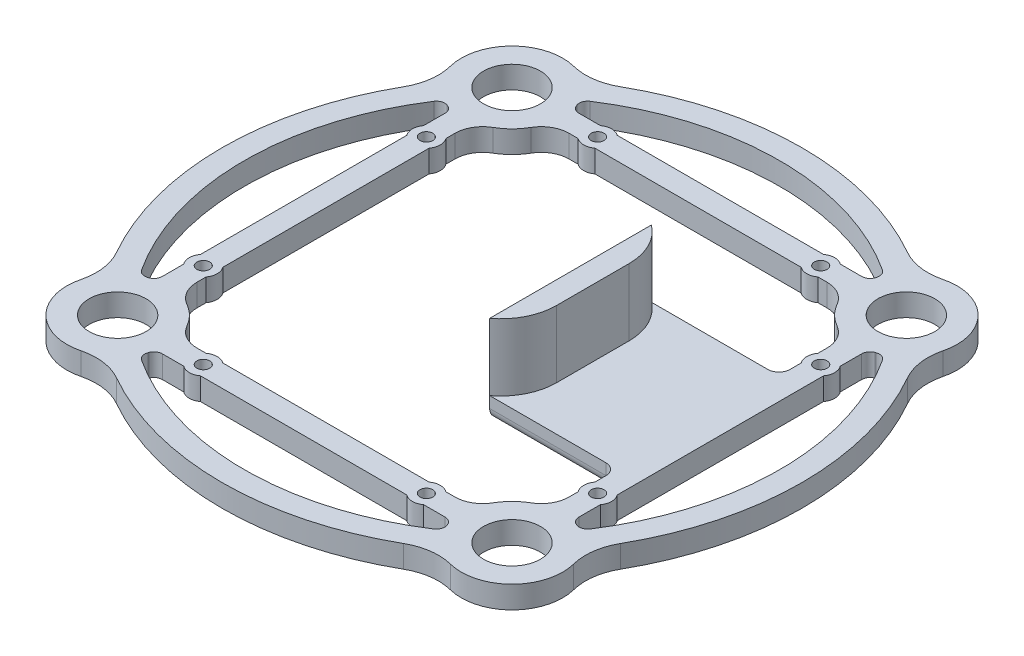
SolidWorks part; units mm, degrees
ref_plane "Front Plane" through (0, 0, 0) normal (0, 0, 1) x (1, 0, 0)
ref_plane "Top Plane" through (0, 0, 0) normal (0, 1, 0) x (1, 0, 0)
ref_plane "Right Plane" through (0, 0, 0) normal (1, 0, 0) x (0, 0, -1)
sketch "Sketch1" plane through (0, 0, 0) normal (0, 1, 0) x (1, 0, 0)
  line L1 (-35.3553, -35.3553) -> (35.3553, -35.3553) construction
  line L2 (-35.3553, -35.3553) -> (-35.3553, 35.3553) construction
  line L3 (-35.3553, 35.3553) -> (35.3553, 35.3553) construction
  line L4 (35.3553, -35.3553) -> (35.3553, 35.3553) construction
  line L5 (-35.3553, -35.3553) -> (35.3553, 35.3553) construction
  line L6 (-35.3553, 35.3553) -> (35.3553, -35.3553) construction
  circle A0 centre (0, 0) radius 52
  circle A1 centre (0, 0) radius 50 construction
  circle A2 centre (0, 0) radius 48
  circle A3 centre (35.3553, 35.3553) radius 5.1
  circle A4 centre (35.3553, 35.3553) radius 9.1
  circle A5 centre (-35.3553, 35.3553) radius 9.1
  circle A6 centre (-35.3553, 35.3553) radius 5.1
  circle A7 centre (-35.3553, -35.3553) radius 9.1
  circle A8 centre (-35.3553, -35.3553) radius 5.1
  circle A9 centre (35.3553, -35.3553) radius 5.1
  circle A10 centre (35.3553, -35.3553) radius 9.1
  dimension "D1" = 96
  dimension "D2" = 100
  dimension "D3" = 104
  dimension "D4" = 10.2
  dimension "D5" = 10.2
  dimension "D6" = 10.2
  dimension "D7" = 10.2
  dimension "D8" = 18.2
  dimension "D9" = 18.2
  dimension "D10" = 18.2
  dimension "D11" = 18.2
extrude "Boss-Extrude1" add sketch "Sketch1" along normal blind 4 contours A7 A2 A5 A0 | A5 A2 A4 A0 | A10 A0 A4 A2 | A10 A2 A7 A0 | A8 A2 A7 | A8 A2 A7 A0 | A8 A0 A7 | A8 A0 A7 A2 | A2 A10 A9 | A0 A10 A2 A9 | A0 A10 A9 | A2 A10 A0 A9 | A0 A4 A2 A3 | A2 A4 A0 A3 | A0 A4 A3 | A2 A4 A3 | A6 A2 A5 A0 | A6 A0 A5 A2 | A6 A0 A5 | A6 A2 A5 region at (49.0102, 0, 15.4585) region at (39.943, 0, -30.075) region at (39.073, 0, -39.073) region at (39.073, 0, 39.073) region at (39.943, 0, 30.075) region at (31.3721, 0, -31.3721) region at (31.3721, 0, 31.3721) region at (30.075, 0, -39.943) region at (0, 0, -48.6096) region at (30.075, 0, 39.943) region at (0, 0, 51.3904) region at (-31.3721, 0, -31.3721) region at (-30.075, 0, -39.943) region at (-39.073, 0, -39.073) region at (-39.073, 0, 39.073) region at (-30.075, 0, 39.943) region at (-31.3721, 0, 31.3721) region at (-41.5843, 0, -27.9071) region at (-39.943, 0, -30.075) region at (-39.943, 0, 30.075)
sketch "Sketch2" plane through (0, 4, 0) normal (0, 1, 0) x (1, 0, 0)
  line L0 (-33.3553, 26.4778) -> (-33.3553, -26.4778)
  line L1 (35.3553, -35.3553) -> (-35.3553, -35.3553) construction
  line L2 (35.3553, -35.3553) -> (35.3553, 35.3553) construction
  line L3 (35.3553, 35.3553) -> (-35.3553, 35.3553) construction
  line L4 (-35.3553, -35.3553) -> (-35.3553, 35.3553) construction
  line L5 (35.3553, -35.3553) -> (-35.3553, 35.3553) construction
  line L6 (35.3553, 35.3553) -> (-35.3553, -35.3553) construction
  line L7 (-37.3553, 26.4778) -> (-37.3553, -26.4778)
  line L8 (-26.4778, 37.3553) -> (26.4778, 37.3553)
  line L9 (-26.4778, 33.3553) -> (26.4778, 33.3553)
  line L10 (37.3553, 26.4778) -> (37.3553, -26.4778)
  line L11 (33.3553, 26.4778) -> (33.3553, -26.4778)
  line L12 (-26.4778, -33.3553) -> (26.4778, -33.3553)
  line L13 (-26.4778, -37.3553) -> (26.4778, -37.3553)
  arc A0 (-39.5091, 27.2586) -> (-27.2586, 39.5091) centre (-35.3553, 35.3553) ccw construction
  arc A1 (-27.2586, -39.5091) -> (-39.5091, -27.2586) centre (-35.3553, -35.3553) ccw construction
  arc A2 (27.2586, 39.5091) -> (39.5091, 27.2586) centre (35.3553, 35.3553) ccw construction
  arc A3 (39.5091, -27.2586) -> (27.2586, -39.5091) centre (35.3553, -35.3553) ccw construction
  circle A4 centre (-35.3553, 35.3553) radius 9.1
  circle A5 centre (35.3553, 35.3553) radius 9.1
  circle A6 centre (35.3553, -35.3553) radius 9.1
  circle A7 centre (-35.3553, -35.3553) radius 9.1
  point P0 (0, 0)
  arc M14 (-27.2586, -39.5091) -> (-39.5091, -27.2586) centre (-35.3553, -35.3553) ccw
  arc M16 (-39.5091, 27.2586) -> (-27.2586, 39.5091) centre (-35.3553, 35.3553) ccw
  arc M18 (27.2586, 39.5091) -> (39.5091, 27.2586) centre (35.3553, 35.3553) ccw
  arc M20 (39.5091, -27.2586) -> (27.2586, -39.5091) centre (35.3553, -35.3553) ccw
  dimension "D1" = 2
  dimension "D2" = 2
  dimension "D3" = 2
  dimension "D4" = 2
  dimension "D5" = 2
  dimension "D6" = 2
  dimension "D7" = 2
  dimension "D8" = 2
extrude "Boss-Extrude2" add sketch "Sketch2" against normal blind 4 contours L9 L8 M16 M18 | L7 L0 M16 M14 | L11 L10 M18 M20 | L13 L12 M14 M20 region at (-35.3553, 4, 0) region at (0, 4, -35.3553) region at (0, 4, 35.3553) region at (35.3553, 4, 0)
sketch "Sketch3" plane through (0, 4, 0) normal (0, 1, 0) x (1, 0, 0)
  line L0 (-26.4778, 33.3553) -> (26.4778, 33.3553) construction
  line L1 (-35.3553, 20) -> (35.3553, 20) construction
  line L2 (-35.3553, 20) -> (-35.3553, -20) construction
  line L3 (-35.3553, -20) -> (35.3553, -20) construction
  line L4 (35.3553, 20) -> (35.3553, -20) construction
  line L5 (-35.3553, 20) -> (35.3553, -20) construction
  line L6 (-35.3553, -20) -> (35.3553, 20) construction
  line L7 (20, -35.3553) -> (-20, -35.3553) construction
  line L8 (20, -35.3553) -> (20, 35.3553) construction
  line L9 (20, 35.3553) -> (-20, 35.3553) construction
  line L10 (-20, -35.3553) -> (-20, 35.3553) construction
  line L11 (20, -35.3553) -> (-20, 35.3553) construction
  line L12 (20, 35.3553) -> (-20, -35.3553) construction
  line L13 (-33.3553, 26.4778) -> (-33.3553, -26.4778) construction
  circle A0 centre (-20, 35.3553) radius 2.5
  circle A1 centre (20, 35.3553) radius 2.5
  circle A2 centre (35.3553, 20) radius 2.5
  circle A3 centre (35.3553, -20) radius 2.5
  circle A4 centre (-35.3553, -20) radius 2.5
  circle A5 centre (-35.3553, 20) radius 2.5
  circle A6 centre (-20, -35.3553) radius 2.5
  circle A7 centre (20, -35.3553) radius 2.5
  point P0 (0, 0)
  point P6 (0, 0)
  dimension "D5" = 5
  dimension "D6" = 5
  dimension "D7" = 5
  dimension "D8" = 5
  dimension "D9" = 5
  dimension "D10" = 5
  dimension "D11" = 5
  dimension "D12" = 5
  dimension "D1" = 2
  dimension "D2" = 2
  dimension "D3" = 40
  dimension "D4" = 40
extrude "Boss-Extrude3" add sketch "Sketch3" against normal blind 4
sketch "Sketch4" plane through (0, 4, 0) normal (0, 1, 0) x (1, 0, 0)
  circle A0 centre (-20, 35.3553) radius 1.15
  circle A1 centre (20, 35.3553) radius 1.15
  circle A2 centre (-35.3553, 20) radius 1.15
  circle A3 centre (-35.3553, -20) radius 1.15
  circle A4 centre (-20, -35.3553) radius 1.15
  circle A5 centre (20, -35.3553) radius 1.15
  circle A6 centre (35.3553, -20) radius 1.15
  circle A7 centre (35.3553, 20) radius 1.15
  dimension "D1" = 2.3
  dimension "D2" = 2.3
  dimension "D3" = 2.3
  dimension "D4" = 2.3
  dimension "D5" = 2.3
  dimension "D6" = 2.3
  dimension "D7" = 2.3
  dimension "D8" = 2.3
extrude "Cut-Extrude1" cut sketch "Sketch4" against normal blind 4
fillet "Fillet1" radius 10 8 edges at (29.8349, 2, 42.5896) (42.5896, 2, 29.8349) (42.5896, 2, -29.8349) (29.8349, 2, -42.5896) (-29.8349, 2, -42.5896) (-42.5896, 2, -29.8349) (-42.5896, 2, 29.8349) (-29.8349, 2, 42.5896)
fillet "Fillet2" radius 1.5 16 edges at (-39.5091, 2, 27.2586) (-37.3553, 2, 26.4778) (-39.5091, 2, -27.2586) (-37.3553, 2, -26.4778) (27.2586, 2, -39.5091) (26.4778, 2, -37.3553) (-26.4778, 2, -37.3553) (-27.2586, 2, -39.5091) (39.5091, 2, 27.2586) (37.3553, 2, 26.4778) (37.3553, 2, -26.4778) (39.5091, 2, -27.2586) (27.2586, 2, 39.5091) (26.4778, 2, 37.3553) (-27.2586, 2, 39.5091) (-26.4778, 2, 37.3553)
fillet "Fillet3" radius 5 8 edges at (-26.4778, 2, -33.3553) (-33.3553, 2, -26.4778) (-33.3553, 2, 26.4778) (-26.4778, 2, 33.3553) (26.4778, 2, 33.3553) (33.3553, 2, 26.4778) (26.4778, 2, -33.3553) (33.3553, 2, -26.4778)
sketch "Sketch5" plane through (0, 4, 0) normal (0, 1, 0) x (1, 0, 0)
  line L5 (33.3553, 18.5) -> (33.3553, -18.5) construction
  line L6 (33.3553, 14.5) -> (10.4953, 14.5)
  line L7 (33.3553, 14.5) -> (33.3553, -14.5)
  line L8 (33.3553, -14.5) -> (10.4953, -14.5)
  line L9 (10.4953, 14.5) -> (10.4953, -14.5)
  circle A0 centre (35.3553, -20) radius 1.15 construction
  dimension "D1" = 22.86
  dimension "D2" = 29
  dimension "D3" = 5.5
extrude "Boss-Extrude4" add sketch "Sketch5" against normal blind 4
sketch "Sketch6" plane through (0, 0, 0) normal (0, -1, 0) x (1, 0, 0)
  line L0 (33.3553, -14.5) -> (10.4953, -14.5) construction
  line L1 (10.4953, 14.5) -> (14.4953, 14.5)
  line L2 (10.4953, 14.5) -> (10.4953, -14.5)
  line L3 (10.4953, -14.5) -> (14.4953, -14.5)
  line L4 (14.4953, 14.5) -> (14.4953, -14.5)
  dimension "D1" = 4
extrude "Boss-Extrude5" add sketch "Sketch6" against normal blind 16
fillet "Fillet4" radius 10 2 edges at (14.4953, 10, -14.5) (14.4953, 10, 14.5)
fillet "Fillet5" radius 2 6 edges at (33.3553, 0, 16.5) (33.3553, 0, -16.5) (21.9253, 0, 14.5) (21.9253, 0, -14.5) (33.3553, 2, -14.5) (33.3553, 2, 14.5)
